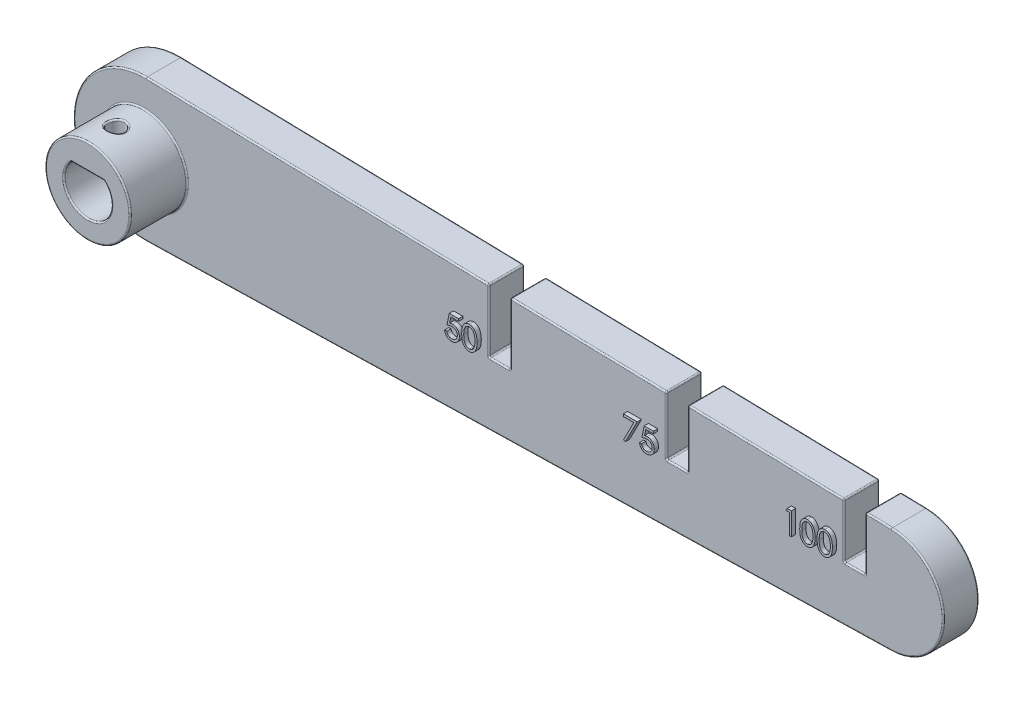
SolidWorks part; units mm, degrees
ref_plane "Front Plane" through (0, 0, 0) normal (0, 0, 1) x (1, 0, 0)
ref_plane "Top Plane" through (0, 0, 0) normal (0, 1, 0) x (1, 0, 0)
ref_plane "Right Plane" through (0, 0, 0) normal (1, 0, 0) x (0, 0, -1)
sketch "Sketch3" plane through (0, 0, 0) normal (0, 0, 1) x (1, 0, 0)
  line L0 (0.2381, 9.9972) -> (105.1786, 7.4979)
  line L1 (105.1786, -7.4979) -> (0.2381, -9.9972)
  arc A0 (0.2381, 9.9972) -> (0.2381, -9.9972) centre (0, 0) ccw
  arc A1 (105.1786, -7.4979) -> (105.1786, 7.4979) centre (105, 0) ccw
  dimension "D1" = 20
  dimension "D2" = 15
  dimension "D3" = 105
extrude "Boss-Extrude1" add sketch "Sketch3" along normal blind 5
sketch "Sketch2" plane through (0, 0, 0) normal (0, 0, 1) x (1, 0, 0)
  line L0 (-2.3, 2.4357) -> (2.3, 2.4357)
  arc A0 (2.3, 2.4357) -> (-2.3, 2.4357) centre (0, 0) cw
  dimension "D1" = 3.35
  dimension "D2" = 4.6
extrude "Cut-Extrude2" cut sketch "Sketch2" along normal up to next
sketch "Sketch4" plane through (0, 0, 5) normal (0, 0, 1) x (1, 0, 0)
  line L0 (105.1786, 7.4979) -> (0.2381, 9.9972) construction
  line L1 (98.5, 7.6569) -> (101.5, 7.6569)
  line L2 (98.5, 7.6569) -> (98.5, 0)
  line L3 (98.5, 0) -> (101.5, 0)
  line L4 (101.5, 7.6569) -> (101.5, 0)
  line L5 (100, 0) -> (100, 7.6212) construction
  line L6 (0, 0) -> (112.5, 0) construction
  line L7 (73.5, 8.2523) -> (76.5, 8.2523)
  line L8 (73.5, 8.2523) -> (73.5, 0)
  line L9 (73.5, 0) -> (76.5, 0)
  line L10 (76.5, 8.2523) -> (76.5, 0)
  line L11 (75, 0) -> (75, 8.2523) construction
  line L12 (48.5, 8.8477) -> (51.5, 8.8477)
  line L13 (48.5, 8.8477) -> (48.5, 0)
  line L14 (48.5, 0) -> (51.5, 0)
  line L15 (51.5, 8.8477) -> (51.5, 0)
  line L16 (50, 0) -> (50, 8.8477) construction
  arc A0 (105.1786, -7.4979) -> (105.1786, 7.4979) centre (105, 0) ccw construction
  dimension "D3" = 3
  dimension "D4" = 50
  dimension "D5" = 75
  dimension "D6" = 100
extrude "Cut-Extrude3" cut sketch "Sketch4" against normal up to next
sketch "Sketch6" plane through (0, 0, 5) normal (0, 0, 1) x (1, 0, 0)
  line L0 (-2.3, 2.4357) -> (2.3, 2.4357)
  circle A0 centre (0, 0) radius 6
  arc A1 (2.3, 2.4357) -> (-2.3, 2.4357) centre (0, 0) cw
  dimension "D1" = 12
extrude "Boss-Extrude3" add sketch "Sketch6" along normal blind 8
sketch "Sketch7" plane through (0, 0, 0) normal (0, 1, 0) x (1, 0, 0)
  line L0 (0, -5) -> (0, -13) construction
  line L1 (-6, -5) -> (6, -5) construction
  line L2 (-6, -13) -> (6, -13) construction
  circle A0 centre (0, -9) radius 1.15
  dimension "D1" = 2.3
extrude "Cut-Extrude4" cut sketch "Sketch7" along normal up to next
fillet "Fillet1" radius 0.2 54 edges at (51.5, 0, 2.5) (48.5, 0, 2.5) (101.5, 0, 2.5) (98.5, 0, 2.5) (76.5, 0, 2.5) (73.5, 0, 2.5) (0, 2.4357, 0) (0, -3.35, 0) (76.5, 4.0904, 0) (75, 0, 0) (73.5, 4.1262, 0) (62.5, 8.5143, 0) (51.5, 4.3881, 0) (50, 0, 0) (48.5, 4.4239, 0) (24.369, 9.4225, 0) (-10, 0, 0) (52.7083, -8.7475, 0) (112.5, 0, 0) (103.3393, 7.5417, 0) (101.5, 3.7927, 0) (100, 0, 0) (98.5, 3.8285, 0) (87.5, 7.9189, 0) (100, 0, 5) (101.5, 3.7927, 5) (103.3393, 7.5417, 5) (112.5, 0, 5) (52.7083, -8.7475, 5) (-10, 0, 5) (24.369, 9.4225, 5) (48.5, 4.4239, 5) (50, 0, 5) (51.5, 4.3881, 5) (62.5, 8.5143, 5) (73.5, 4.1262, 5) (75, 0, 5) (76.5, 4.0904, 5) (87.5, 7.9189, 5) (98.5, 3.8285, 5) (101.5, 7.5855, 2.5) (98.5, 7.6569, 2.5) (76.5, 8.1809, 2.5) (73.5, 8.2523, 2.5) (51.5, 8.7763, 2.5) (48.5, 8.8477, 2.5) (6, 0, 5) (0, 2.4357, 13) (2.3, 2.4357, 6.5) (0, -3.35, 13) (-2.3, 2.4357, 6.5) (-0.241, 5.9952, 10.1245) (0, 2.4357, 7.85) (6, 0, 13)
sketch "Sketch5" plane through (0, 0, 5) normal (0, 0, 1) x (1, 0, 0)
  line L0 (0, 0) -> (112.3, 0) construction
  line L1 (48.5, 8.6525) -> (48.5, 0.2) construction
  line L2 (73.5, 8.057) -> (73.5, 0.2) construction
  line L3 (98.5, 7.4616) -> (98.5, 0.2) construction
  arc A0 (105.1738, -7.2979) -> (105.1738, 7.2979) centre (105, 0) ccw construction
  text T0 "50"
  text T1 "75"
  text T2 "100"
  dimension "D1" = 5.8
  dimension "D2" = 5.8
  dimension "D3" = 8.2
extrude "Boss-Extrude2" add sketch "Sketch5" along normal blind 0.6
